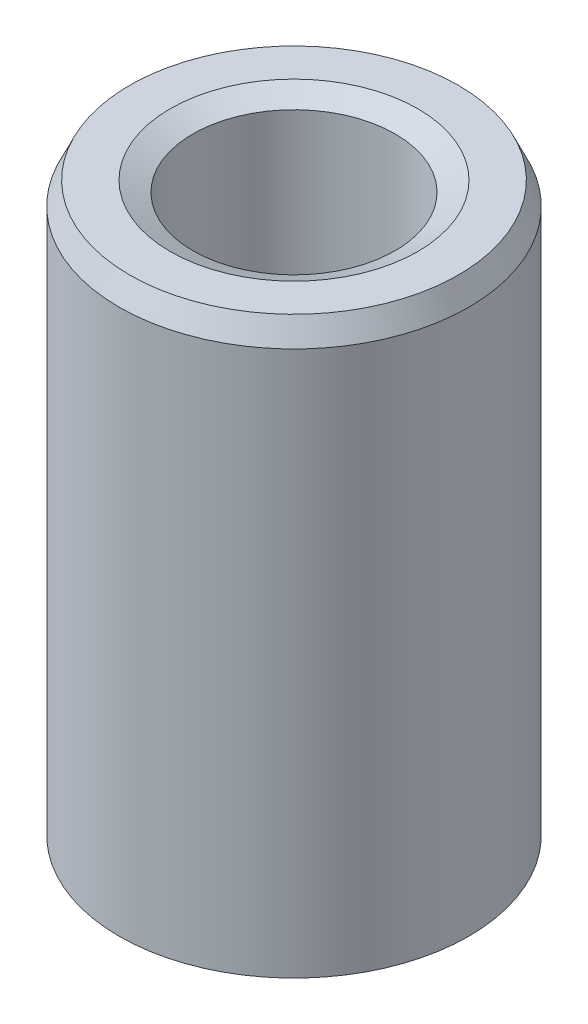
SolidWorks part; units mm, degrees
ref_plane "Front Plane" through (0, 0, 0) normal (0, 0, 1) x (1, 0, 0)
ref_plane "Top Plane" through (0, 0, 0) normal (0, 1, 0) x (1, 0, 0)
ref_plane "Right Plane" through (0, 0, 0) normal (1, 0, 0) x (0, 0, -1)
sketch "Sketch1" plane through (0, 0, 0) normal (0, 1, 0) x (1, 0, 0)
  circle A0 centre (0, 0) radius 7.5
  dimension "SLEEVE_OD" = 15
extrude "Boss-Extrude1" add sketch "Sketch1" along normal blind 24.7899
sketch "Sketch2" plane through (0, 0, 0) normal (0, 1, 0) x (1, 0, 0)
  circle A0 centre (0, 0) radius 4.3395
  dimension "BORE_D" = 8.679
extrude "Cut-Extrude1" cut sketch "Sketch2" along normal through all
chamfer "Chamfer1" distance 0.969 angle 24.985 4 edges at (0, 24.7899, 4.3395) (0, 0, 4.3395) (0, 0, 7.5) (0, 24.7899, 7.5) first distance on face at (0, 24.7899, 4.3395) first distance on face at (0, 0, 4.3395) first distance on face at (0, 24.7899, 7.5)
